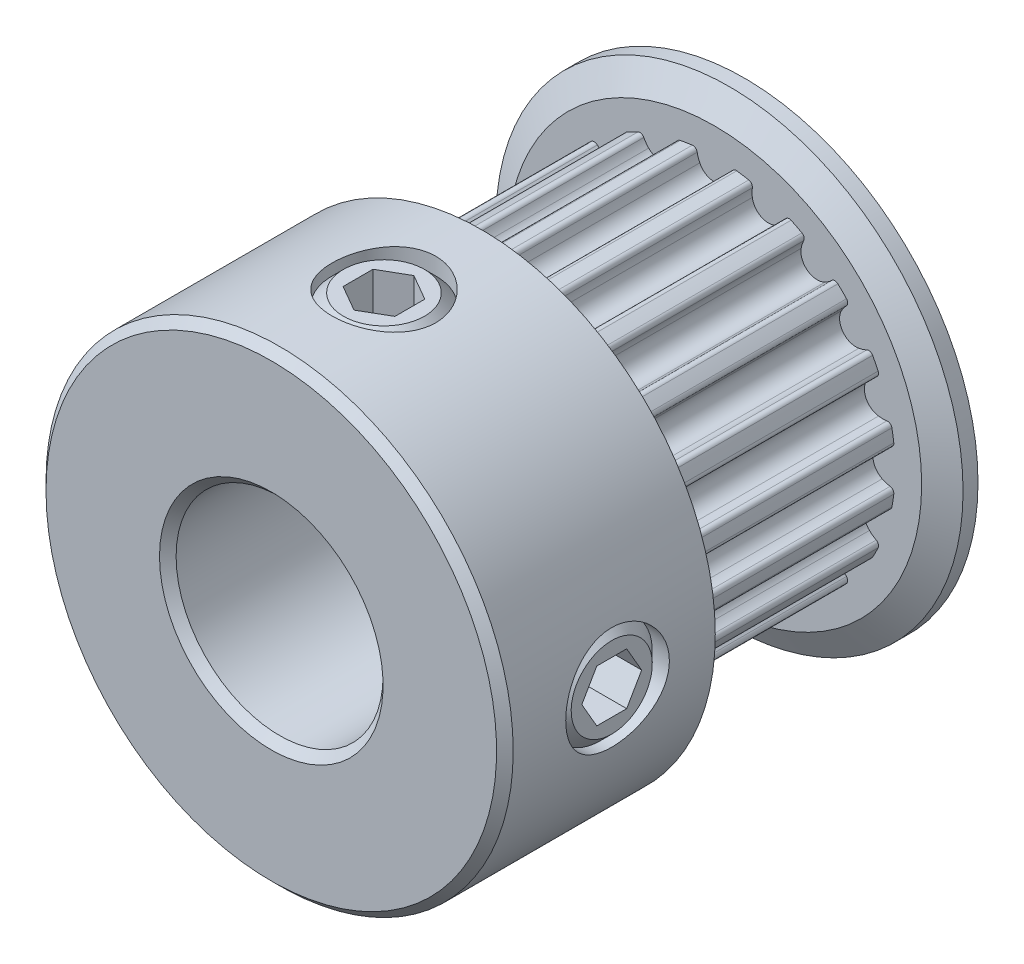
SolidWorks part; units mm, degrees
material "6061-T6 (SS)"
ref_plane "Front Plane" through (0, 0, 0) normal (0, 0, 1) x (1, 0, 0)
ref_plane "Top Plane" through (0, 0, 0) normal (0, 1, 0) x (1, 0, 0)
ref_plane "Right Plane" through (0, 0, 0) normal (1, 0, 0) x (0, 0, -1)
sketch "Sketch1" plane through (0, 0, 0) normal (0, 0, 1) x (1, 0, 0)
  line L1 (-1.7499, 5.3585) -> (1.7499, 5.3585) construction
  line L4 (0, 0) -> (0, 5.3585) construction
  line L5 (0, 5.3585) -> (0, 11.2111) construction
  line L6 (0, 6.3625) -> (1.9751, 6.0482) construction
  line L7 (1.9751, 6.0482) -> (2.6648, 5.8229) construction
  line L8 (1.9751, 6.0482) -> (1.7499, 5.3585) construction
  line L9 (-1.9751, 6.0482) -> (-1.7499, 5.3585) construction
  line L10 (-1.8963, 5.8067) -> (-2.5799, 7.9)
  line L11 (-2.5799, 7.9) -> (2.5799, 7.9)
  line L12 (2.5799, 7.9) -> (1.8963, 5.8067)
  circle A0 centre (0, 0) radius 6.3625 construction
  circle A1 centre (0, 0) radius 7.9 construction
  circle A2 centre (0, 0) radius 6.1085 construction
  arc A3 (-0.4989, 5.6703) -> (0.4989, 5.6703) centre (0, 5.9135) ccw
  arc A4 (-0.4989, 5.6703) -> (-0.5855, 5.9387) centre (0.4, 6.1085) cw
  arc A5 (-1.8963, 5.8067) -> (-0.7518, 6.0621) centre (0, 0) cw
  arc A6 (-0.5855, 5.9387) -> (-0.7518, 6.0621) centre (-0.7333, 5.9132) ccw
  arc A7 (1.8963, 5.8067) -> (0.7518, 6.0621) centre (0, 0) ccw
  arc A8 (0.5855, 5.9387) -> (0.7518, 6.0621) centre (0.7333, 5.9132) cw
  arc A9 (0.4989, 5.6703) -> (0.5855, 5.9387) centre (-0.4, 6.1085) ccw
  point P6 (0, 20.9083)
  point P11 (0, 6.3625)
  point P13 (0, 7.9)
  point P14 (0, 6.1085)
  dimension "D1" = 9.6972
  dimension "D2" = 4.8486
sketch "Sketch2" plane through (0, 0, 0) normal (1, 0, 0) x (0, 0, -1)
  line L0 (-8, 3.5) -> (8, 3.5)
  line L1 (-8, 3.5) -> (-8, 7.9)
  line L2 (-0.885, 7.9) -> (-8, 7.9)
  line L3 (-1.39, 3.5) -> (-1.39, 7.9) construction
  line L4 (-1.39, 7.9) -> (-0.38, 7.9) construction
  line L5 (-0.38, 7.9) -> (-0.38, 6.1085) construction
  line L6 (-0.38, 6.1085) -> (6.99, 6.1085)
  line L7 (6.99, 6.1085) -> (6.99, 7.9) construction
  line L8 (6.99, 7.9) -> (8, 7.9) construction
  line L9 (8, 7.9) -> (8, 3.5)
  line L10 (-8, 0) -> (8, 0) construction
  line L11 (7.495, 7.9) -> (6.99, 7.0042)
  line L12 (-0.38, 7.0042) -> (-0.885, 7.9)
  line L14 (-0.38, 7.0042) -> (-0.38, 6.1085)
  line L15 (6.99, 6.1085) -> (6.99, 7.0042)
  line L16 (7.495, 7.9) -> (8, 7.9)
  arc A0 (-0.38, 7.0042) -> (-0.885, 7.9) centre (-1.4269, 7.0042) ccw construction
  arc A1 (6.99, 7.0042) -> (7.495, 7.9) centre (8.0369, 7.0042) cw construction
  point P12 (-0.38, 7.0042)
  point P14 (-0.885, 7.9)
  point P20 (6.99, 7.0042)
  point P21 (7.495, 7.9)
  point P25 (6.99, 0)
  point P26 (-0.38, 0)
  dimension "OA" = 16
  dimension "Bore" = 7
  dimension "Outside Width" = 8.38
  dimension "Inside Width" = 7.37
revolve "Revolve1" add sketch "Sketch2" angle 360 mid plane about L10
sketch "Sketch3" plane through (0, 0, 0) normal (0, 0, 1) x (1, 0, 0)
  line L6 (2.5799, 7.9) -> (-2.5799, 7.9)
  line L7 (1.8963, 5.8067) -> (2.5799, 7.9)
  line L8 (-2.5799, 7.9) -> (-1.8963, 5.8067)
  line L9 (2.5799, 7.9) -> (-2.5799, 7.9)
  line L10 (1.8963, 5.8067) -> (2.5799, 7.9)
  line L11 (-2.5799, 7.9) -> (-1.8963, 5.8067)
  arc A8 (1.8963, 5.8067) -> (0.7518, 6.0621) centre (0, 0) ccw
  arc A9 (0.7518, 6.0621) -> (0.5855, 5.9387) centre (0.7333, 5.9132) ccw
  arc A10 (0.4989, 5.6703) -> (0.5855, 5.9387) centre (-0.4, 6.1085) ccw
  arc A11 (-0.4989, 5.6703) -> (0.4989, 5.6703) centre (0, 5.9135) ccw
  arc A12 (-0.5855, 5.9387) -> (-0.4989, 5.6703) centre (0.4, 6.1085) ccw
  arc A13 (-0.5855, 5.9387) -> (-0.7518, 6.0621) centre (-0.7333, 5.9132) ccw
  arc A14 (-0.7518, 6.0621) -> (-1.8963, 5.8067) centre (0, 0) ccw
  arc A15 (1.8963, 5.8067) -> (0.7518, 6.0621) centre (0, 0) ccw
  arc A16 (0.7518, 6.0621) -> (0.5855, 5.9387) centre (0.7333, 5.9132) ccw
  arc A17 (0.4989, 5.6703) -> (0.5855, 5.9387) centre (-0.4, 6.1085) ccw
  arc A18 (-0.4989, 5.6703) -> (0.4989, 5.6703) centre (0, 5.9135) ccw
  arc A19 (-0.5855, 5.9387) -> (-0.4989, 5.6703) centre (0.4, 6.1085) ccw
  arc A20 (-0.5855, 5.9387) -> (-0.7518, 6.0621) centre (-0.7333, 5.9132) ccw
  arc A21 (-0.7518, 6.0621) -> (-1.8963, 5.8067) centre (0, 0) ccw
  dimension "D1" = 0
extrude "Cut-Extrude1" cut sketch "Sketch3" against normal up to vertex (6.99 mm away) from vertex up to point (0, 6.1085, -6.99) starting at point (0, 6.1085, 0.38)
pattern_circular "CirPattern1" count 20 over 360 about axis through (0, 0, 8) along (0, 0, 1) of "Cut-Extrude1"
sketch "Sketch4" plane through (0, 0, 0) normal (1, 0, 0) x (0, -1, 0)
  line L0 (0, -0.38) -> (0, -8) construction
  line L1 (-3.5, -8) -> (3.5, -8) construction
  line L2 (7.0042, -0.38) -> (-7.0042, -0.38) construction
  circle A0 centre (0, -4.19) radius 1.7526
extrude "Cut-Extrude2" cut sketch "Sketch4" along normal through all
ref_plane "Plane1" through (0, 0, 4.19) normal (0, 0, 1) x (1, 0, 0)
sketch "Sketch5" plane through (0, 0, 4.19) normal (0, 0, 1) x (1, 0, 0)
  line L0 (0, 0) -> (0, 7.9) construction
  line L1 (3.5, -1.3716) -> (3.5, 0)
  line L2 (3.881, -1.7526) -> (7.3221, -1.7526)
  line L3 (3.5, 0) -> (7.9, 0) construction
  line L4 (3.5, 0) -> (7.7031, 0)
  line L5 (7.7031, 0) -> (7.7031, -1.3716)
  line L6 (3.881, -1.7526) -> (3.5, -1.3716)
  line L7 (7.7031, -1.3716) -> (7.3221, -1.7526)
  circle A0 centre (0, 0) radius 7.9 construction
  circle A1 centre (0, 0) radius 3.5 construction
  point P2 (3.5, -1.7526)
  point P11 (7.7031, -1.7526)
revolve "Revolve2" add sketch "Sketch5" angle 360 mid plane about L4
sketch "Sketch6" plane through (7.7031, 5.3841, 0) normal (-1, 0, 0) x (0, -1, 0)
  line L1 (5.3841, 5.2019) -> (4.5078, 4.6959)
  line L2 (4.5078, 4.6959) -> (4.5078, 3.6841)
  line L3 (4.5078, 3.6841) -> (5.3841, 3.1781)
  line L4 (5.3841, 3.1781) -> (6.2604, 3.6841)
  line L5 (6.2604, 3.6841) -> (6.2604, 4.6959)
  line L6 (6.2604, 4.6959) -> (5.3841, 5.2019)
  circle A0 centre (5.3841, 4.19) radius 0.8763 construction
  dimension "D1" = 1.7526
extrude "Cut-Extrude3" cut sketch "Sketch6" along normal blind 1.3144
pattern_circular "CirPattern3" count 2 over 90 about axis through (0, 0, 8) along (0, 0, 1) of "Cut-Extrude2", "Revolve2", "Cut-Extrude3"
chamfer "Chamfer1" distance 0.2807 angle 45 2 edges at (3.5, 0, 8) (7.9, 0, 8)
ref_axis "Center Axis 1" through (0, 0, -8) along (0, 0, 1)
ref_plane "Contact Plane 1" through (0, 0, 8) normal (0, 0, 1) x (1, 0, 0)
ref_plane "Contact Plane 2" through (0, 0, -8) normal (0, 0, -1) x (-1, 0, 0)
equation "\"D2@Sketch1\"= \"D1@Sketch1\" / 2"
equation "\"D1@Sketch6\" = \"Set Screw@Sketch4\" / 2"
equation "\"D1@Cut-Extrude3\" = \"D1@Sketch6\"*.75"
